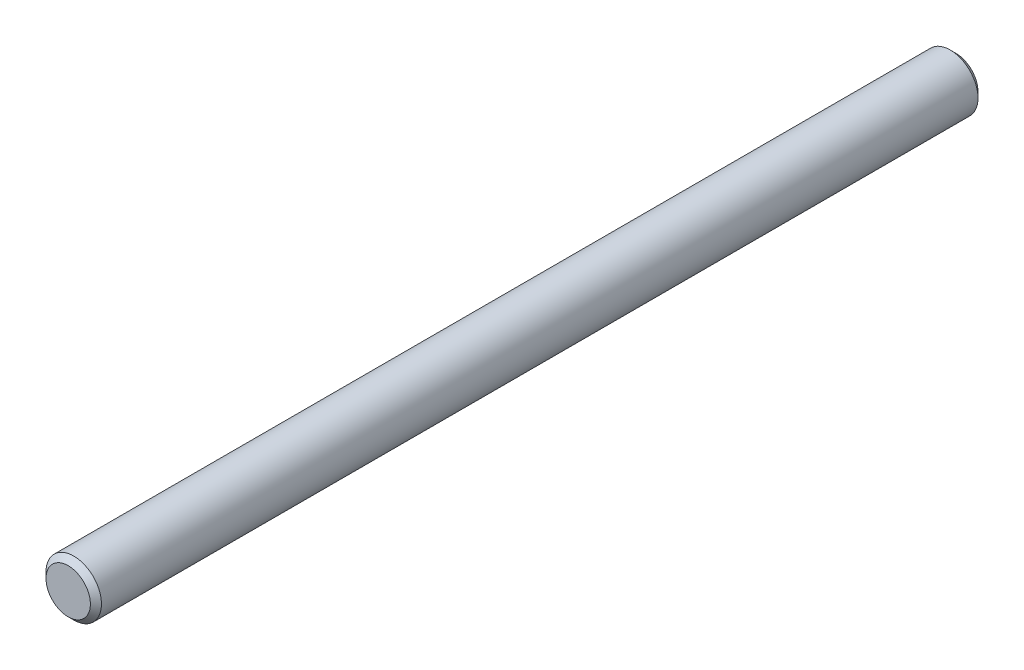
SolidWorks part; units mm, degrees
ref_plane "Front" through (0, 0, 0) normal (0, 0, 1) x (1, 0, 0)
ref_plane "Top" through (0, 0, 0) normal (0, 1, 0) x (1, 0, 0)
ref_plane "Right" through (0, 0, 0) normal (1, 0, 0) x (0, 0, -1)
sketch "Sketch1" plane through (0, 0, 0) normal (0, 0, 1) x (1, 0, 0)
  circle A0 centre (0, 0) radius 9.525
  dimension "dia" = 19.05
extrude "Extrude1" add sketch "Sketch1" along normal mid plane 304.8
sketch "Sketch2" plane through (0, 0, 0) normal (1, 0, 0) x (0, 0, -1)
  line L0 (152.4, 9.525) -> (149.9, 9.525) construction
  line L1 (152.4, 9.525) -> (-152.4, 9.525) construction
  line L2 (149.9, 9.525) -> (111.8, 9.525) construction
  line L3 (111.8, 9.525) -> (109.8, 9.525) construction
  line L4 (109.8, 9.525) -> (99.8, 9.525) construction
  line L5 (99.8, 9.525) -> (97.9, 9.525) construction
  line L6 (111.8, 9.525) -> (111.8, -9.4601) construction
  line L7 (99.8, 9.525) -> (-65.2, 9.525) construction
  line L8 (-65.2, 9.525) -> (-67.2, 9.525) construction
  line L9 (-67.2, 9.525) -> (-67.2, -9.525) construction
  line L10 (-152.4, -9.525) -> (152.4, -9.525) construction
  line L11 (-152.4, 9.525) -> (-149.9, 9.525) construction
  line L12 (-149.9, 9.525) -> (-149.9, -9.525) construction
  point P0 (-152.4, 9.525)
  point P1 (152.4, 9.525)
  dimension "D1" = 2.5
  dimension "D2" = 38.1
  dimension "D3" = 2
  dimension "D4" = 10
  dimension "D5" = 1.9
  dimension "D6" = 165
  dimension "D7" = 2
  dimension "D8" = 2.5
chamfer "Chamfer1" distance 1.905 angle 45 2 edges at (9.525, 0, -152.4) (9.525, 0, 152.4)
equation "\"D1@Chamfer1\" = \"dia@Sketch1\" * .1"
